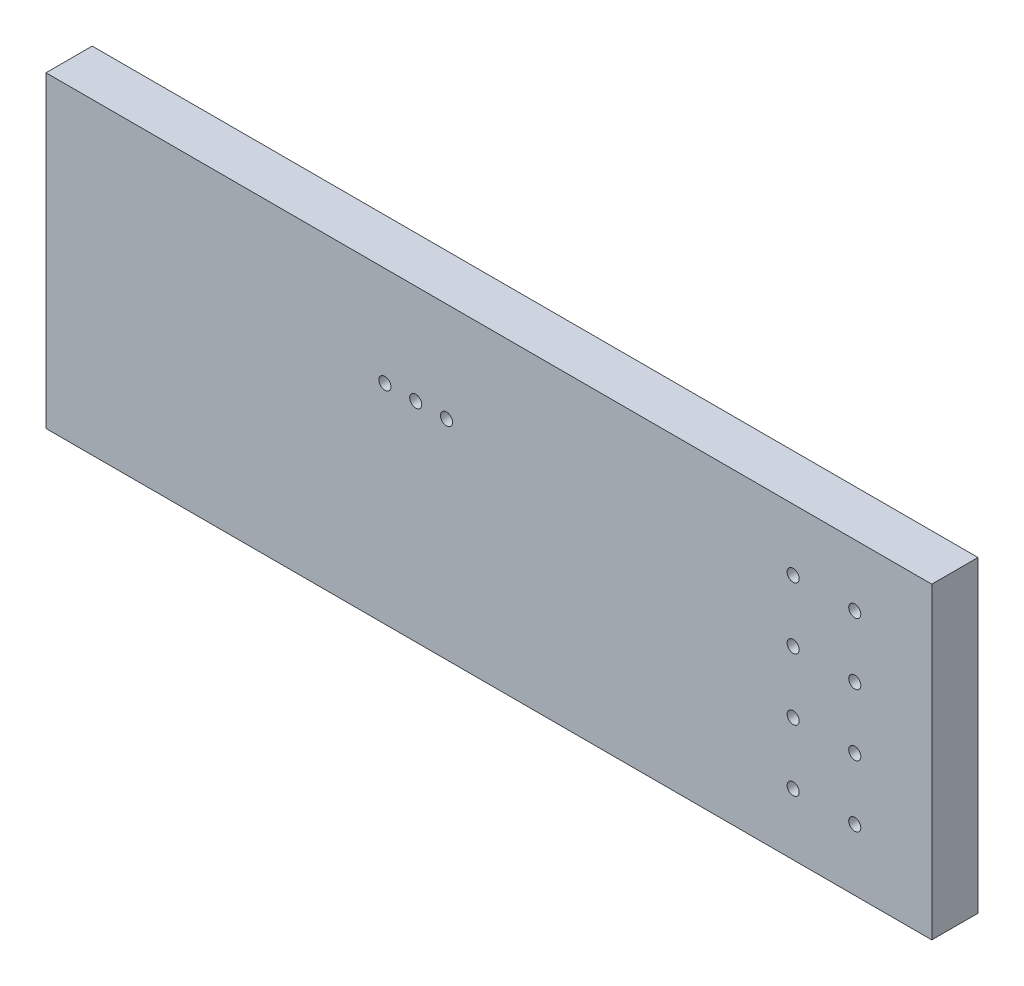
SolidWorks part; units mm, degrees
material "Pine"
ref_plane "Front Plane" through (0, 0, 0) normal (0, 0, 1) x (1, 0, 0)
ref_plane "Top Plane" through (0, 0, 0) normal (0, 1, 0) x (1, 0, 0)
ref_plane "Right Plane" through (0, 0, 0) normal (1, 0, 0) x (0, 0, -1)
sketch "Sketch1" plane through (0, 0, 0) normal (0, 0, 1) x (1, 0, 0)
  line L1 (0, 0) -> (717.55, 0)
  line L2 (0, 0) -> (0, 127)
  line L3 (0, 127) -> (717.55, 127)
  line L4 (717.55, 0) -> (717.55, 127)
  line L6 (717.55, 0) -> (717.55, 127)
  line L9 (0, 127) -> (-19.05, 127)
  line L10 (0, 127) -> (0, 0)
  line L11 (0, 0) -> (-19.05, 0)
  line L12 (-19.05, 127) -> (-19.05, 0)
  dimension "D1" = 717.55
  dimension "D2" = 127
  dimension "D3" = 19.05
extrude "Boss-Extrude1" add sketch "Sketch1" along normal blind 19.05 contours L1 L4 L3 L2 region at (358.775, 63.5, 0)
sketch "Sketch2" plane through (0, 0, 19.05) normal (0, 0, 1) x (1, 0, 0)
  line L3 (0, 0) -> (0, 127) construction
  line L4 (0, 127) -> (717.55, 127) construction
  line L5 (717.55, 0) -> (717.55, 127) construction
  circle A0 centre (12.7, 101.6) radius 2.4892
  circle A1 centre (38.1, 101.6) radius 2.4892
  circle A2 centre (38.1, 76.2) radius 2.4892
  circle A3 centre (38.1, 50.8) radius 2.4892
  circle A4 centre (38.1, 25.4) radius 2.4892
  circle A5 centre (12.7, 76.2) radius 2.4892
  circle A6 centre (12.7, 50.8) radius 2.4892
  circle A7 centre (12.7, 25.4) radius 2.4892
  circle A8 centre (685.8, 101.6) radius 2.4892
  circle A9 centre (660.4, 101.6) radius 2.4892
  circle A10 centre (660.4, 76.2) radius 2.4892
  circle A11 centre (660.4, 50.8) radius 2.4892
  circle A12 centre (660.4, 25.4) radius 2.4892
  circle A13 centre (685.8, 76.2) radius 2.4892
  circle A14 centre (685.8, 50.8) radius 2.4892
  circle A15 centre (685.8, 25.4) radius 2.4892
  dimension "D1" = 4.9784
  dimension "D2" = 25.4
  dimension "D3" = 12.7
  dimension "D6" = 25.4
  dimension "D7" = 31.75
  dimension "D8" = 4.9784
  dimension "D11" = 25.4
  dimension "D12" = 25.4
  dimension "D13" = 25.4
  dimension "D14" = 25.4
  dimension "D4" = 2
  dimension "D5" = 4
  dimension "D9" = 2
  dimension "D10" = 4
extrude "Cut-Extrude1" cut sketch "Sketch2" against normal blind 25.4
sketch "Sketch4" plane through (0, 0, 19.05) normal (0, 0, 1) x (1, 0, 0)
  line L0 (180.975, 85.979) -> (206.375, 85.979) construction
  line L1 (0, 127) -> (717.55, 127) construction
  line L2 (492.125, 85.979) -> (517.525, 85.979) construction
  line L3 (206.375, 85.979) -> (492.125, 85.979) construction
  line L4 (-19.05, 127) -> (717.55, 127) construction
  line L5 (-19.05, 127) -> (-19.05, 0) construction
  circle A0 centre (180.975, 85.979) radius 2.4892
  circle A1 centre (193.675, 85.979) radius 2.4892
  circle A2 centre (206.375, 85.979) radius 2.4892
  circle A3 centre (492.125, 85.979) radius 2.4892
  circle A4 centre (504.825, 85.979) radius 2.4892
  circle A5 centre (517.525, 85.979) radius 2.4892
  point P21 (349.25, 127)
  point P22 (349.25, 85.979)
  dimension "D1" = 4.9784
  dimension "D2" = 41.021
  dimension "D4" = 4.9784
  dimension "D6" = 41.021
  dimension "D7" = 285.75
  dimension "D3" = 12.7
  dimension "D5" = 12.7
extrude "Cut-Extrude2" cut sketch "Sketch4" against normal through all
sketch "Sketch5" plane through (0, 0, 19.05) normal (0, 0, 1) x (1, 0, 0)
  line L0 (0, 127) -> (717.55, 127) construction
  line L1 (0, 0) -> (352.425, 0)
  line L2 (0, 0) -> (0, 127)
  line L3 (0, 127) -> (352.425, 127)
  line L4 (352.425, 0) -> (352.425, 127)
  line L5 (717.55, 0) -> (717.55, 127) construction
  dimension "D1" = 365.125
extrude "Cut-Extrude3" cut sketch "Sketch5" against normal through all
